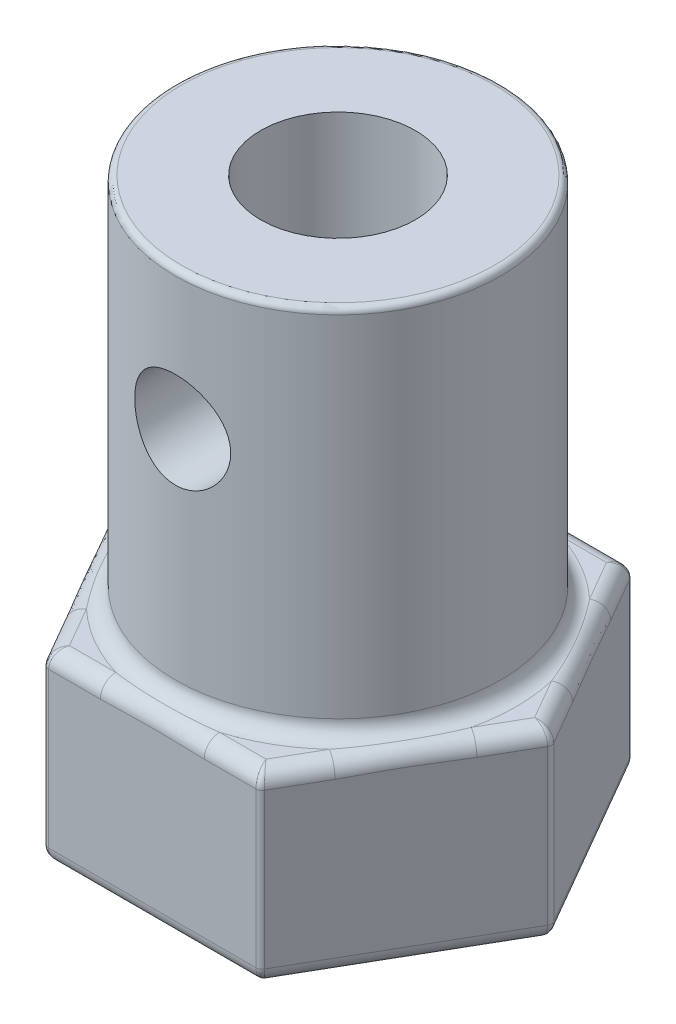
SolidWorks part; units mm, degrees
ref_plane "前视基准面" through (0, 0, 0) normal (0, 0, 1) x (1, 0, 0)
ref_plane "上视基准面" through (0, 0, 0) normal (0, 1, 0) x (1, 0, 0)
ref_plane "右视基准面" through (0, 0, 0) normal (1, 0, 0) x (0, 0, -1)
sketch "草图1" plane through (0, 0, 0) normal (0, 1, 0) x (1, 0, 0)
  line L1 (6.9282, 0) -> (3.4641, 6)
  line L2 (3.4641, 6) -> (-3.4641, 6)
  line L3 (-3.4641, 6) -> (-6.9282, 0)
  line L4 (-6.9282, 0) -> (-3.4641, -6)
  line L5 (-3.4641, -6) -> (3.4641, -6)
  line L6 (3.4641, -6) -> (6.9282, 0)
  circle A0 centre (0, 0) radius 6 construction
  circle A1 centre (0, 0) radius 2
  dimension "D2" = 4
  dimension "D1" = 12
extrude "凸台-拉伸1" add sketch "草图1" along normal blind 6
sketch "草图2" plane through (0, 6, 0) normal (0, 1, 0) x (1, 0, 0)
  circle A0 centre (0, 0) radius 5.25
  circle A1 centre (0, 0) radius 2.5
  dimension "D1" = 10.5
  dimension "D2" = 5
extrude "凸台-拉伸2" add sketch "草图2" along normal blind 12
sketch "草图3" plane through (0, 0, 0) normal (0, 0, 1) x (1, 0, 0)
  line L0 (5.25, 18) -> (-5.25, 18) construction
  circle A0 centre (0, 13.5) radius 1.55
  dimension "D2" = 3.1
  dimension "D1" = 4.5
extrude "切除-拉伸1" cut sketch "草图3" against normal through all both and the other way through all
fillet "圆角1" radius 0.5 1 edges at (0, 6, 5.25)
fillet "圆角2" radius 0.5 12 edges at (5.1962, 0, -3) (5.1962, 0, 3) (0, 0, 6) (-5.1962, 0, 3) (-5.1962, 0, -3) (0, 0, -6) (5.1962, 6, 3) (0, 6, 6) (-5.1962, 6, 3) (-5.1962, 6, -3) (0, 6, -6) (5.1962, 6, -3)
fillet "圆角3" radius 0.2 18 edges at (-3.3796, 0.1464, 5.8536) (-6.7591, 0.1464, 0) (3.3796, 0.1464, 5.8536) (-3.3796, 0.1464, -5.8536) (6.7591, 0.1464, 0) (3.3796, 0.1464, -5.8536) (6.9282, 3, 0) (3.4641, 3, 6) (3.4641, 3, -6) (-3.4641, 3, 6) (-6.9282, 3, 0) (-3.4641, 3, -6) (-3.3796, 5.8536, -5.8536) (-6.7591, 5.8536, 0) (3.3796, 5.8536, -5.8536) (-3.3796, 5.8536, 5.8536) (6.7591, 5.8536, 0) (3.3796, 5.8536, 5.8536)
fillet "圆角4" radius 0.2 1 edges at (0, 18, 5.25)
